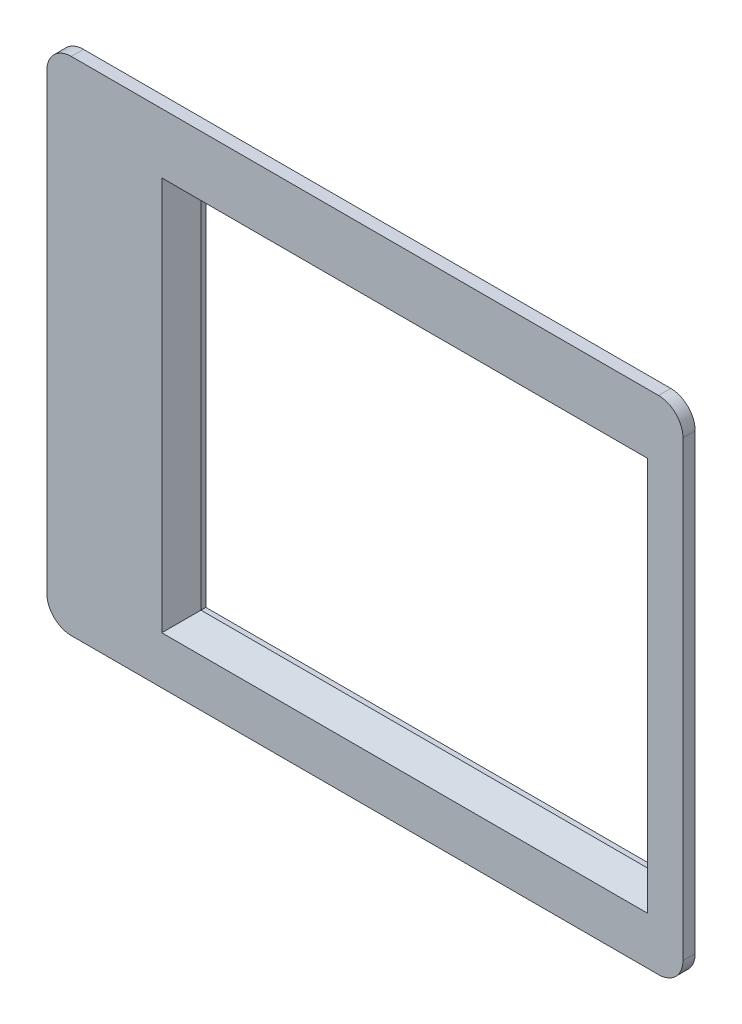
SolidWorks part; units mm, degrees
ref_plane "Спереди" through (0, 0, 0) normal (0, 0, 1) x (1, 0, 0)
ref_plane "Сверху" through (0, 0, 0) normal (0, 1, 0) x (1, 0, 0)
ref_plane "Справа" through (0, 0, 0) normal (1, 0, 0) x (0, 0, -1)
sketch "Эскиз1" plane through (0, 0, 0) normal (0, 0, 1) x (1, 0, 0)
  line L1 (0, 0) -> (46, 0)
  line L2 (0, 0) -> (0, 35)
  line L3 (0, 35) -> (46, 35)
  line L4 (46, 0) -> (46, 35)
  line L5 (-3, -3) -> (49, -3)
  line L6 (-3, -3) -> (-3, 38)
  line L7 (-3, 38) -> (49, 38)
  line L8 (49, -3) -> (49, 38)
  line L9 (8, 2.5) -> (44.5, 2.5)
  line L10 (8, 2.5) -> (8, 31.5)
  line L11 (8, 31.5) -> (44.5, 31.5)
  line L12 (44.5, 2.5) -> (44.5, 31.5)
  point P9 (49, 17.5)
  dimension "D1" = 46
  dimension "D2" = 35
  dimension "D3" = 3
  dimension "D4" = 3
  dimension "D5" = 3
  dimension "D6" = 3
  dimension "D7" = 8
  dimension "D8" = 3.5
  dimension "D9" = 1.5
  dimension "D10" = 2.5
extrude "Бобышка-Вытянуть1" add sketch "Эскиз1" against normal blind 1 contours L5 L8 L7 L6 L4 L1 L2 L3 region at (-2.3378, 17.5, 0)
extrude "Бобышка-Вытянуть2" add sketch "Эскиз1<3>" against normal blind 2 contours L1 L4 L3 L2 L12 L9 L10 L11 region at (0.578, 17.5, 0)
sketch "Эскиз1<3>" plane through (0, 0, 0) normal (0, 0, 1) x (1, 0, 0) same geometry as "Эскиз1"
fillet "Скругление2" radius 2 8 edges at (-3, -3, -0.5) (0, 0, -1.5) (49, -3, -0.5) (46, 0, -1.5) (49, 38, -0.5) (46, 35, -1.5) (-3, 38, -0.5) (0, 35, -1.5)
chamfer "Фаска1" distance 1.6 angle 45 4 edges at (26.25, 2.5, 0) (44.5, 17, 0) (8, 17, 0) (26.25, 31.5, 0)
